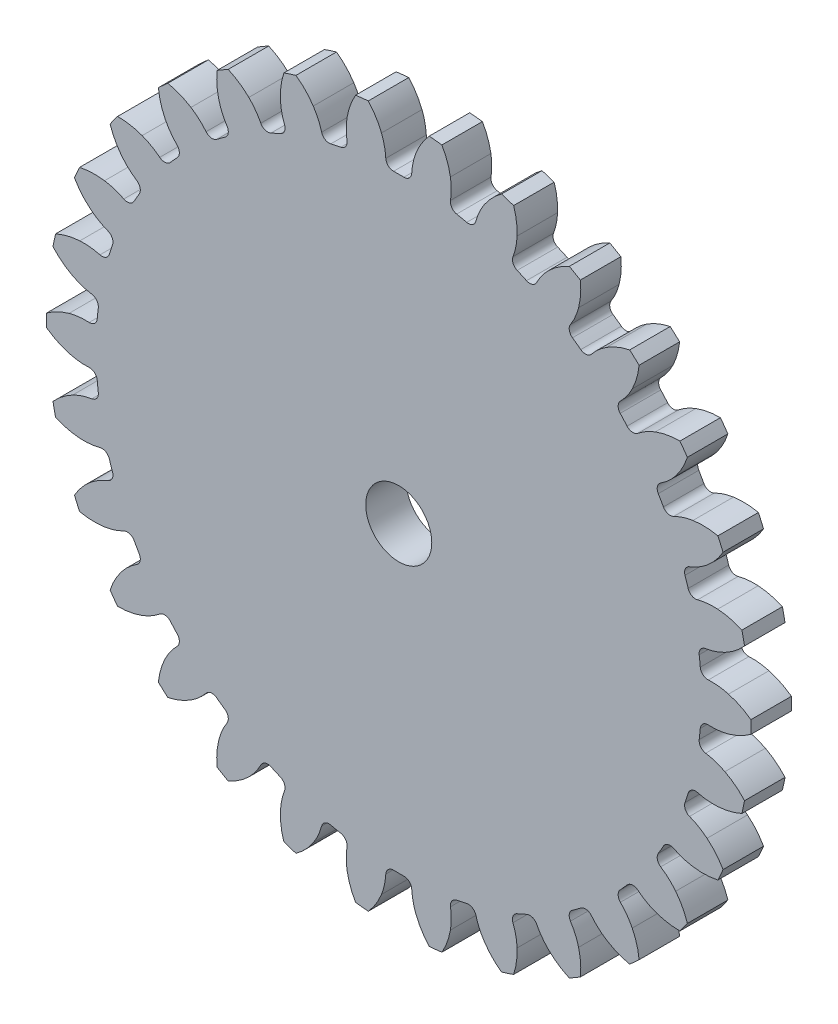
SolidWorks part; units mm, degrees
ref_plane "Front Plane" through (0, 0, 0) normal (0, 0, 1) x (1, 0, 0)
ref_plane "Top Plane" through (0, 0, 0) normal (0, 1, 0) x (1, 0, 0)
ref_plane "Right Plane" through (0, 0, 0) normal (1, 0, 0) x (0, 0, -1)
sketch "Sketch1" plane through (0, 0, 0) normal (0, 0, 1) x (1, 0, 0)
  line L0 (0, 0) -> (47.625, 0) construction
  line L1 (47.625, 0) -> (50.8, 0) construction
  circle A0 centre (0, 0) radius 50.8
  circle A1 centre (0, 0) radius 47.625 construction
  dimension "D2" = 95.25
  dimension "D1" = 3.175
extrude "GEAR_BASE" add sketch "Sketch1" along normal mid plane 5.842
sketch "Sketch2" plane through (0, 0, 2.921) normal (0, 0, 1) x (1, 0, 0)
  line L0 (0, 0) -> (43.6562, 0) construction
  line L1 (43.6562, 0) -> (47.625, 0) construction
  line L2 (0, 0) -> (-50.8, 0) construction
  line L3 (0, 0) -> (-47.5597, -2.494) construction
  line L4 (-47.5597, -2.494) -> (-48.4854, 15.1594) construction
  line L5 (0, 0) -> (-49.6899, -10.5619) construction
  line L6 (-47.5597, -2.494) -> (-43.5589, -2.9143) construction
  line L7 (-47.0389, -7.4487) -> (-43.2129, -6.2057) construction
  line L8 (0, 0) -> (-47.0389, -7.4487) construction
  line L9 (-47.5597, -2.494) -> (-50.7917, -0.9177) construction
  line L10 (-47.0389, -7.4487) -> (-49.8726, -9.6625) construction
  line L11 (-47.0389, -7.4487) -> (-46.5204, -9.8882) construction
  line L12 (-47.0389, -7.4487) -> (-44.274, -24.9088) construction
  line L13 (-47.5597, -2.494) -> (-47.5597, 0) construction
  circle A0 centre (0, 0) radius 47.625 construction
  circle A1 centre (0, 0) radius 43.6562 construction
  circle A2 centre (0, 0) radius 50.8 construction
  arc A3 (-49.8726, -9.6625) -> (-50.7917, -0.9177) centre (0, 0) cw
  arc A4 (-43.4883, -3.8254) -> (-44.6549, -2.8132) centre (-44.5953, -3.9228) ccw
  arc A5 (-44.264, -6.5326) -> (-43.3334, -5.2999) centre (-44.4364, -5.4348) ccw
  arc A6 (-43.3334, -5.2999) -> (-43.4883, -3.8254) centre (0, 0) cw
  arc A7 (-49.8726, -9.6625) -> (-47.0389, -7.4487) centre (-42.4148, -16.2882) cw
  arc A8 (-50.7917, -0.9177) -> (-47.5597, -2.494) centre (-44.8744, 7.1137) ccw
  arc A9 (-47.0389, -7.4487) -> (-44.264, -6.5326) centre (-42.8676, -15.4226) cw
  arc A10 (-47.5597, -2.494) -> (-44.6549, -2.8132) centre (-45.1374, 6.173) ccw
  dimension "D1" = 95.25
  dimension "D11" = 1.1112
  dimension "D12" = 9.9758
  dimension "D2" = 3.9688
  dimension "D3" = 12
  dimension "D5" = 9
  dimension "D7" = 9
  dimension "D8" = 4.9821
  dimension "D9" = 20
  dimension "D10" = 20
  dimension "D6" = 2.494
  dimension "D4" = 2.494
extrude "GEAR_CUT" cut sketch "Sketch2" against normal through all
ref_axis "GEAR_AXIS" through (0, 0, -3.2131) along (0, 0, 1)
pattern_circular "GEAR_TEETH" count 30 over 360 about axis through (0, 0, -3.2131) along (0, 0, 1) of "GEAR_CUT"
sketch "Sketch3" plane through (0, 0, 2.921) normal (0, 0, 1) x (1, 0, 0)
  circle A0 centre (0, 0) radius 4.7625
  dimension "D1" = 9.525
extrude "BORE" cut sketch "Sketch3" against normal through all
equation "\"N_teeth\" = 30"
equation "\"pitch_diameter\"= \"N_teeth\" / \"Pitch\""
equation "\"Pitch\"= 8"
equation "\"addendum\"=1.000/\"Pitch\""
equation "\"face_width\"=0.23"
equation "\"deddendum\"=1.250/\"Pitch\""
equation "\"tooth_thickness\"=1.571/\"Pitch\""
equation "\"Pressure_Angle\"=20.000000"
equation "\"base_fillet\"=0.35/\"Pitch\""
equation "\"D1@Sketch1\"=\"addendum\""
equation "\"D2@Sketch1\"=\"pitch_diameter\""
equation "\"D1@GEAR_BASE\" = \"face_width\""
equation "\"D1@Sketch2\"= \"pitch_diameter\""
equation "\"D2@Sketch2\"=\"deddendum\""
equation "\"D4@Sketch2\"=\"tooth_thickness\"/2"
equation "\"D6@Sketch2\"=\"tooth_thickness\"/2"
equation "\"D9@Sketch2\"=\"Pressure_Angle\""
equation "\"D10@Sketch2\"=\"Pressure_Angle\""
equation "\"D11@Sketch2\"=\"base_fillet\""
equation "\"D12@Sketch2\"=2*\"tooth_thickness\""
equation "\"D3@Sketch2\" = 360 / \"N_teeth\""
equation "\"D1@GEAR_TEETH\" = \"N_teeth\""
